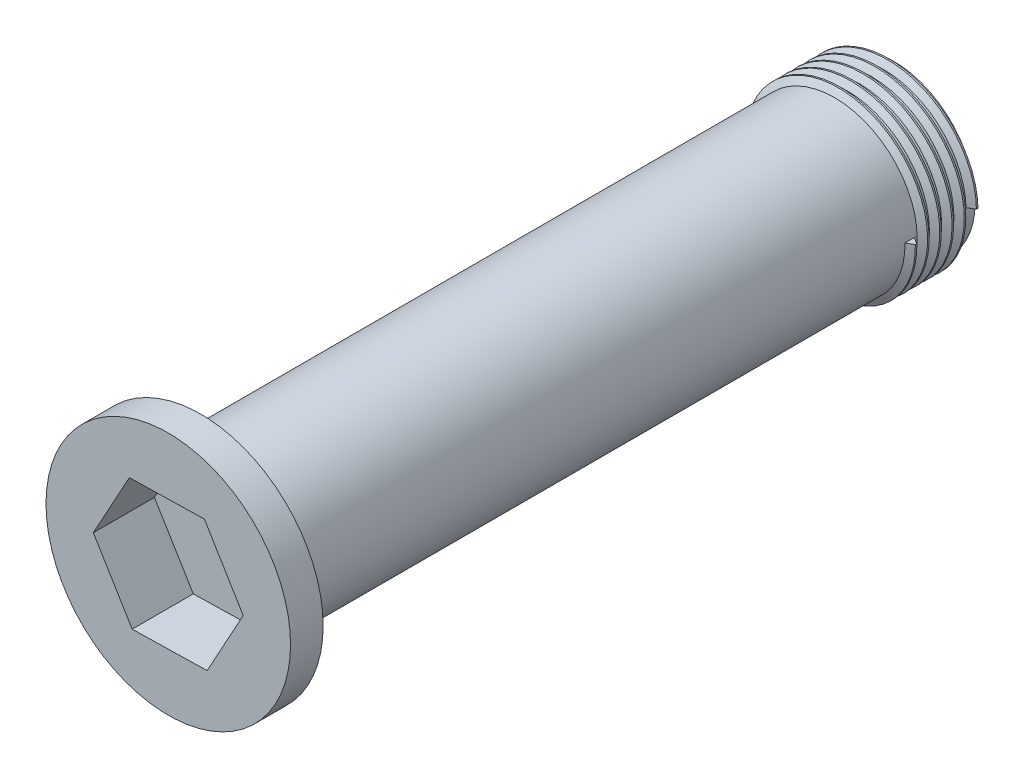
SolidWorks part; units mm, degrees
material "AISI 304"
ref_plane "Alzado" through (0, 0, 0) normal (0, 0, 1) x (1, 0, 0)
ref_plane "Planta" through (0, 0, 0) normal (0, 1, 0) x (1, 0, 0)
ref_plane "Vista lateral" through (0, 0, 0) normal (1, 0, 0) x (0, 0, -1)
ref_plane "Plano1" through (0, 0, 51.9) normal (0, 0, 1) x (1, 0, 0)
sketch "Sk_Cana" plane through (0, 0, 51.9) normal (0, 0, 1) x (1, 0, 0)
  circle A0 centre (0, 0) radius 2
extrude "Cana" add sketch "Sk_Cana" along normal blind 17
ref_plane "Plano2" through (0, 0, 68.9) normal (0, 0, 1) x (1, 0, 0)
sketch "Sk_Cabeza" plane through (0, 0, 68.9) normal (0, 0, 1) x (1, 0, 0)
  circle A0 centre (0, 0) radius 3
extrude "Cabeza" add sketch "Sk_Cabeza" along normal blind 0.8
sketch "Croquis1" plane through (0, 0, 51.9) normal (0, 0, -1) x (-1, 0, 0)
  circle A1 centre (0, 0) radius 2
  circle A2 centre (0, 0) radius 2
  dimension "D1" = 0
thread "Rosca1" pitch 0.3 method extrude profile "Perfil de rosca2" start angle 0, offset 0, length 0, pitch 0.3, diameter 4
ref_plane "Plano4" through (2, 0, 51.9) normal (0, -1, 0) x (1, 0, 0)
sketch "Perfil de rosca2" plane through (2, 0, 51.9) normal (0, -1, 0) x (1, 0, 0)
  line L0 (0, 0) -> (0, 0.3) construction
  line L1 (0, 0) -> (0.1624, 0.0937)
  line L2 (0.1624, 0.0937) -> (0.1624, 0.1312)
  line L3 (0.1624, 0.1312) -> (0, 0.225)
  line L4 (0.1624, 0.1125) -> (0, 0.1125) construction
  line L11 (0, 0) -> (0, 0.225)
  point P2 (0, 0)
  dimension "Pitch" = 0.3
  dimension "Profile_Angle" = 60
  dimension "Profile_Land" = 0.0375
  dimension "Profile_Height" = 0.1624
sketch "Croquis9" plane through (0, 0, 69.7) normal (0, 0, 1) x (1, 0, 0)
  line L1 (0.886, 1.6125) -> (-0.9535, 1.5735)
  line L2 (-0.9535, 1.5735) -> (-1.8395, -0.039)
  line L3 (-1.8395, -0.039) -> (-0.886, -1.6125)
  line L4 (-0.886, -1.6125) -> (0.9535, -1.5735)
  line L5 (0.9535, -1.5735) -> (1.8395, 0.039)
  line L6 (1.8395, 0.039) -> (0.886, 1.6125)
  circle A0 centre (0, 0) radius 1.5934 construction
extrude "Cortar-Extruir1" cut sketch "Croquis9" against normal blind 1.5
